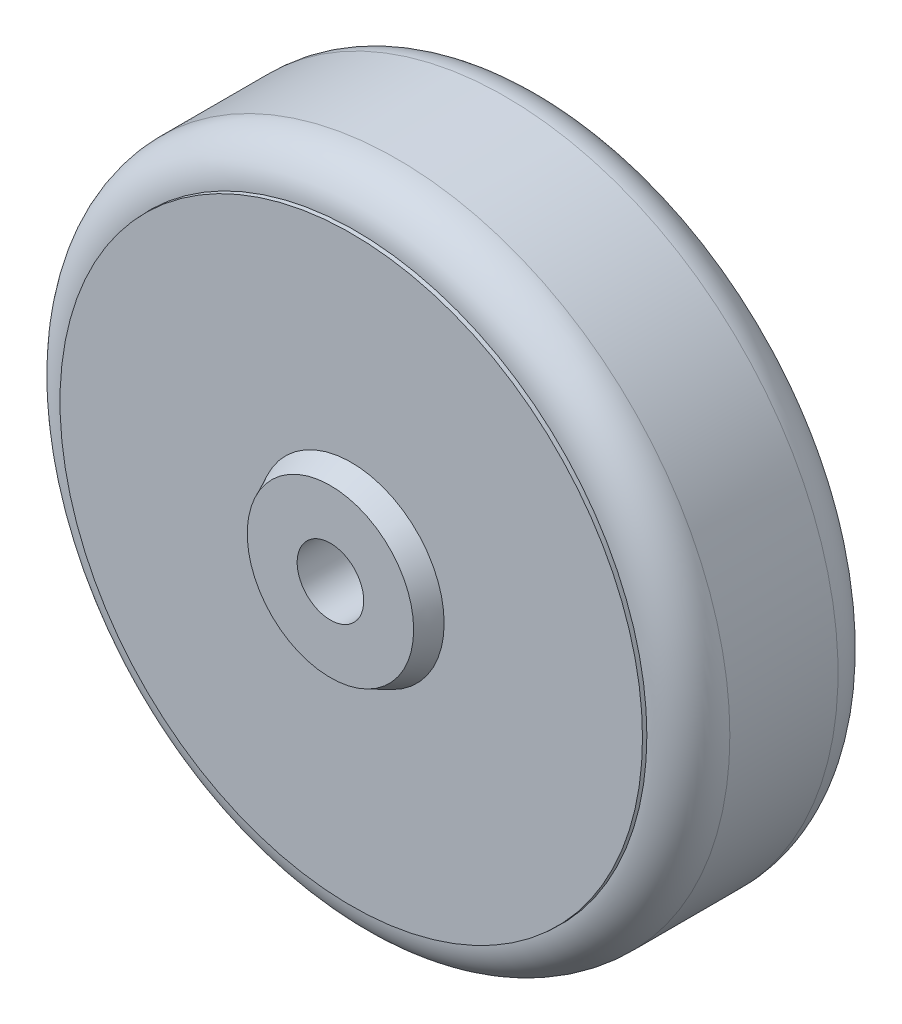
SolidWorks part; units mm, degrees
material "Natural Rubber"
ref_plane "Front Plane" through (0, 0, 0) normal (0, 0, 1) x (1, 0, 0)
ref_plane "Top Plane" through (0, 0, 0) normal (0, 1, 0) x (1, 0, 0)
ref_plane "Right Plane" through (0, 0, 0) normal (1, 0, 0) x (0, 0, -1)
sketch "Sketch1" plane through (0, 0, 0) normal (0, 0, 1) x (1, 0, 0)
  circle A0 centre (0, 0) radius 80
  dimension "D1" = 160
extrude "Boss-Extrude1" add sketch "Sketch1" along normal blind 62
sketch "Sketch2" plane through (0, 0, 62) normal (0, 0, 1) x (1, 0, 0)
  circle A0 centre (0, 0) radius 8
  dimension "D1" = 16
sketch "Sketch3" plane through (0, 0, 0) normal (0, 0, -1) x (-1, 0, 0)
  circle A0 centre (0, 0) radius 54
  dimension "D1" = 108
extrude "Cut-Extrude1" cut sketch "Sketch3" against normal blind 10 draft 45 flip side to cut
sketch "Sketch4" plane through (0, 0, 62) normal (0, 0, 1) x (1, 0, 0)
  circle A0 centre (0, 0) radius 20
  dimension "D1" = 40
extrude "Cut-Extrude2" cut sketch "Sketch4" against normal blind 5 draft 25 flip side to cut contours A0
sketch "Sketch5" plane through (0, 0, 0) normal (0, 0, -1) x (-1, 0, 0)
  line L0 (10.9703, 10.23) -> (36.5677, 34.0999)
  line L1 (6.3393, 13.5946) -> (21.1309, 45.3154)
  line L2 (-6.3393, 13.5946) -> (-21.1309, 45.3154)
  line L3 (14.8882, -1.828) -> (49.6273, -6.0935)
  line L4 (13.1193, -7.2721) -> (43.731, -24.2405)
  line L5 (2.8621, -14.7244) -> (9.5404, -49.0814)
  line L6 (-2.8621, -14.7244) -> (-9.5404, -49.0814)
  line L7 (-13.1193, -7.2721) -> (-43.731, -24.2405)
  line L8 (-14.8882, -1.828) -> (-49.6273, -6.0935)
  line L9 (-10.9703, 10.23) -> (-36.5677, 34.0999)
  arc A0 (-36.5677, 34.0999) -> (-49.6273, -6.0935) centre (0, 0) ccw
  arc A1 (-6.3393, 13.5946) -> (-10.9703, 10.23) centre (0, 0) ccw
  arc A2 (-14.8882, -1.828) -> (-13.1193, -7.2721) centre (0, 0) ccw
  arc A3 (10.9703, 10.23) -> (6.3393, 13.5946) centre (0, 0) ccw
  arc A4 (13.1193, -7.2721) -> (14.8882, -1.828) centre (0, 0) ccw
  arc A5 (-2.8621, -14.7244) -> (2.8621, -14.7244) centre (0, 0) ccw
  arc A6 (21.1309, 45.3154) -> (-21.1309, 45.3154) centre (0, 0) ccw
  arc A7 (49.6273, -6.0935) -> (36.5677, 34.0999) centre (0, 0) ccw
  arc A8 (9.5404, -49.0814) -> (43.731, -24.2405) centre (0, 0) ccw
  arc A9 (-43.731, -24.2405) -> (-9.5404, -49.0814) centre (0, 0) ccw
  point P26 (0, 0)
  dimension "D1" = 100
  dimension "D2" = 30
  dimension "D3" = 5
extrude "Cut-Extrude3" cut sketch "Sketch5" against normal blind 2
sketch "Sketch6" plane through (0, 0, 57) normal (0, 0, 1) x (1, 0, 0)
  circle A0 centre (0, 0) radius 70
  dimension "D1" = 140
extrude "Cut-Extrude4" cut sketch "Sketch6" against normal blind 1 draft 3 flip side to cut
fillet "Fillet1" radius 10 3 edges at (-64, 0, 10) (80, 0, 56) (-80, 0, 10)
extrude "Cut-Extrude5" cut sketch "Sketch2" against normal blind 50
